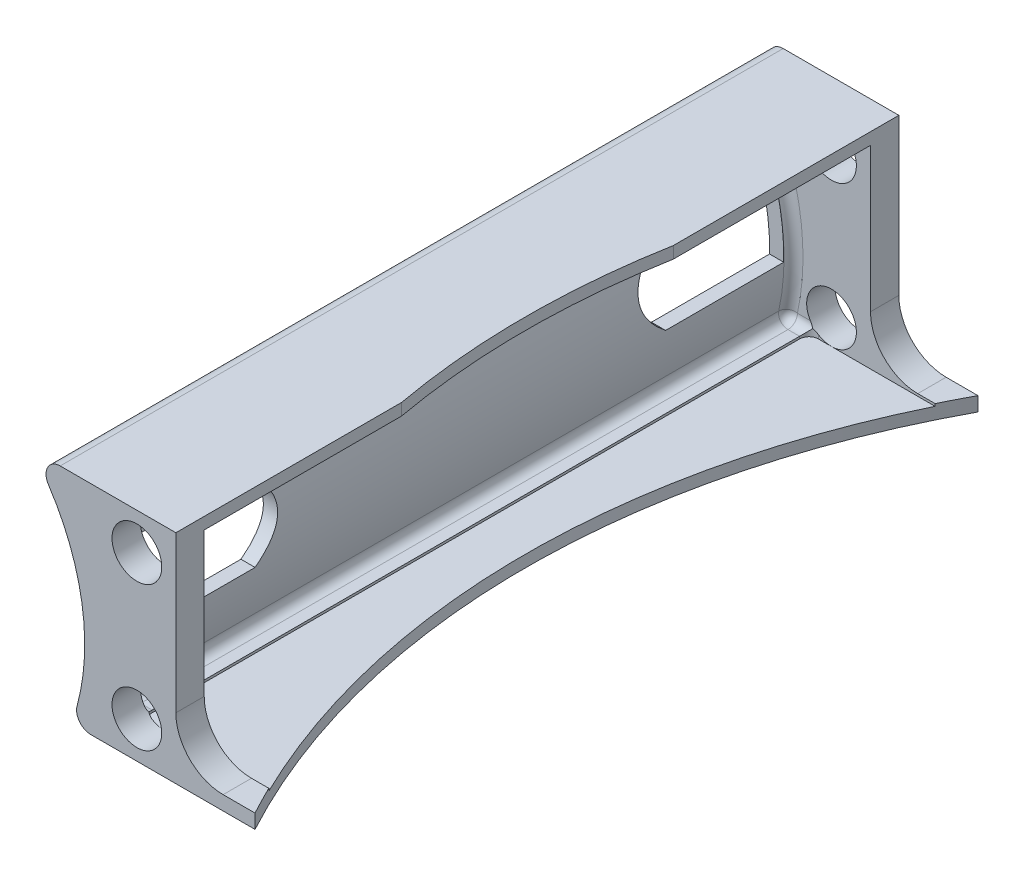
SolidWorks part; units mm, degrees
ref_plane "Alzado" through (0, 0, 0) normal (0, 0, 1) x (1, 0, 0)
ref_plane "Planta" through (0, 0, 0) normal (0, 1, 0) x (1, 0, 0)
ref_plane "Vista lateral" through (0, 0, 0) normal (1, 0, 0) x (0, 0, -1)
sketch "Croquis1" plane through (0, 0, 0) normal (0, 0, 1) x (1, 0, 0)
  line L0 (0, 0) -> (250, 0) construction
  line L1 (47.2783, -15.875) -> (82.0398, -15.875)
  line L2 (40.8073, 30.125) -> (82.0398, 30.125)
  line L3 (43.1739, -15.875) -> (0, -15.875) construction
  line L4 (53.5698, 30.125) -> (53.5698, 22.947) construction
  line L5 (0, 0) -> (0, 34.925) construction
  line L6 (82.0398, 30.125) -> (82.0398, -15.875)
  line L7 (34.7633, 30.125) -> (-5.6174, 14.8479) construction
  line L8 (-5.5, 6.4807) -> (-5.5, -6.4807) construction
  line L9 (5.5, 6.4807) -> (5.5, -6.4807) construction
  arc A0 (-5.5, -6.4807) -> (5.5, -6.4807) centre (0, 0) ccw construction
  circle A2 centre (0, 0) radius 15.875 construction
  arc A5 (44.3837, -12.0867) -> (38.3089, 25.4643) centre (0, 0) ccw
  arc A6 (5.5, 6.4807) -> (-5.5, 6.4807) centre (0, 0) ccw construction
  arc A7 (47.2783, -15.875) -> (44.3837, -12.0867) centre (47.2783, -12.875) cw
  arc A8 (38.3089, 25.4643) -> (40.8073, 30.125) centre (40.8073, 27.125) cw
  dimension "D1" = 17
  dimension "D3" = 3
  dimension "D4" = 31.75
  dimension "D5" = 92
  dimension "D2" = 250
  dimension "D6" = 46
  dimension "D7" = 12.7625
  dimension "D8" = 28.47
  dimension "D9" = 5.5
extrude "Saliente-Extruir1" add sketch "Croquis1" along normal blind 6
sketch "Croquis6" plane through (0, 0, 0) normal (0, 0, -1) x (-1, 0, 0)
  line L0 (-61.4235, 30.125) -> (-61.4235, -15.875) construction
  line L1 (-82.0398, 30.125) -> (-40.8073, 30.125) construction
  line L2 (-47.2783, -15.875) -> (-82.0398, -15.875) construction
  line L3 (-45.8073, 27.125) -> (-40.8073, 27.125)
  line L4 (-47.2783, -12.875) -> (-52.2783, -12.875)
  line L5 (-45.8073, 27.125) -> (-45.8073, 30.125)
  line L6 (-45.8073, 30.125) -> (-40.8073, 30.125)
  line L7 (-52.2783, -12.875) -> (-52.2783, -15.875)
  line L8 (-52.2783, -15.875) -> (-47.2783, -15.875)
  arc A9 (-38.3089, 25.4643) -> (-40.8073, 30.125) centre (-40.8073, 27.125) ccw
  arc A10 (-38.3089, 25.4643) -> (-44.3837, -12.0867) centre (0, 0) ccw
  arc A11 (-40.8073, 27.125) -> (-47.2783, -12.875) centre (0, 0) ccw
  arc A12 (-40.8073, 27.125) -> (-47.2783, -12.875) centre (0, 0) ccw
  arc A13 (-47.2783, -15.875) -> (-44.3837, -12.0867) centre (-47.2783, -12.875) ccw
  arc A14 (-38.3089, 25.4643) -> (-40.8073, 30.125) centre (-40.8073, 27.125) ccw
  arc A15 (-38.3089, 25.4643) -> (-44.3837, -12.0867) centre (0, 0) ccw
  arc A16 (-47.2783, -15.875) -> (-44.3837, -12.0867) centre (-47.2783, -12.875) ccw
  dimension "D1" = 3
  dimension "D2" = 5
  dimension "D3" = 5
  dimension "D4" = 0
extrude "Saliente-Extruir4" add sketch "Croquis6" along normal blind 141
sketch "Croquis7" plane through (0, 0, -141) normal (0, 0, -1) x (-1, 0, 0)
  line L0 (-82.0398, 30.125) -> (-40.8073, 30.125)
  line L1 (-82.0398, 30.125) -> (-82.0398, -15.875)
  line L2 (-82.0398, -15.875) -> (-47.2783, -15.875)
  arc A9 (-47.2783, -15.875) -> (-44.3837, -12.0867) centre (-47.2783, -12.875) ccw
  arc A10 (-38.3089, 25.4643) -> (-44.3837, -12.0867) centre (0, 0) ccw
  arc A11 (-38.3089, 25.4643) -> (-40.8073, 30.125) centre (-40.8073, 27.125) ccw
  arc A12 (-47.2783, -15.875) -> (-44.3837, -12.0867) centre (-47.2783, -12.875) ccw
  arc A13 (-38.3089, 25.4643) -> (-44.3837, -12.0867) centre (0, 0) ccw
  arc A14 (-38.3089, 25.4643) -> (-40.8073, 30.125) centre (-40.8073, 27.125) ccw
  dimension "D1" = 0
extrude "Saliente-Extruir5" add sketch "Croquis7" along normal blind 6
fillet "Redondeo10" radius 2 8 edges at (43.3073, 27.125, -141) (43.3073, 27.125, 0) (49.7783, -12.875, 0) (49.7783, -12.875, -141) (40.8073, 27.125, -70.5) (47.2783, -12.875, -70.5) (48.3711, 7.8252, -141) (48.3711, 7.8252, 0)
fillet "Redondeo11" radius 2 4 edges at (45.8073, 27.625, 0) (52.2783, -13.375, 0) (52.2783, -13.375, -141) (45.8073, 27.625, -141)
sketch "Croquis8" plane through (0, 0, -147) normal (0, 0, -1) x (-1, 0, 0)
  line L0 (-82.0398, 27.125) -> (-37.8073, 27.125) construction
  line L1 (-82.0398, 30.125) -> (-82.0398, -15.875) construction
  line L2 (-40.8073, 30.125) -> (-82.0398, 30.125) construction
  line L6 (-40.8073, 30.125) -> (-40.8073, 27.125) construction
  line L7 (-48.8073, 27.125) -> (-48.8073, 24.5529) construction
  line L8 (-47.2783, -15.875) -> (-52.2783, -15.875) construction
  line L9 (-82.0398, -15.875) -> (-47.2783, -15.875) construction
  line L10 (-82.0398, -12.875) -> (-57.0408, -12.875) construction
  line L11 (-52.2783, -15.875) -> (-52.2783, 0) construction
  line L12 (-45.8073, 30.125) -> (-45.8073, 27.125) construction
  line L24 (-82.0398, -3.5688) -> (-82.0398, -4.3625)
  line L26 (-57.0408, -8.1125) -> (-82.0398, -8.1125) construction
  line L35 (-82.0398, -12.875) -> (-82.0398, -11.8625)
  line L36 (-82.0398, 7.125) -> (-33.2045, 7.125) construction
  arc A0 (-38.3089, 25.4643) -> (-40.8073, 30.125) centre (-40.8073, 27.125) ccw construction
  circle A3 centre (-57.0408, -8.1125) radius 5.2625
  circle A4 centre (-47.2783, -12.875) radius 3 construction
  arc A5 (-47.2783, -15.875) -> (-44.3837, -12.0867) centre (-47.2783, -12.875) ccw construction
  circle A7 centre (-57.0408, 22.3625) radius 5.2625
  point P22 (-40.8073, 28.625)
  point P32 (-59.9766, -8.1125)
  dimension "D5" = 10.525
  dimension "D7" = 5
  dimension "D10" = 30.475
  dimension "D1" = 3
  dimension "D4" = 8
  dimension "D6" = 3
  dimension "D8" = 5
  dimension "D9" = 7.5
extrude "Cortar-Extruir5" cut sketch "Croquis8" against normal blind 161 contours A3 | A7 region at (57.0408, -8.1125, -147)
sketch "Croquis9" plane through (82.0398, 0, 0) normal (1, 0, 0) x (0, 0, -1)
  line L0 (141, 7.125) -> (0, 7.125) construction
  line L1 (141, 30.125) -> (141, -15.875) construction
  line L3 (70.5, 7.125) -> (70.5, -15.875) construction
  line L4 (139, -15.875) -> (2, -15.875) construction
  line L8 (138.937, 15.125) -> (138.937, -0.9147)
  line L11 (2.063, 15.125) -> (2.063, -0.9147)
  line L12 (138.937, -0.9147) -> (113.937, -0.9147)
  line L13 (2.063, 15.125) -> (27.063, 15.125)
  line L14 (2.063, -0.9147) -> (27.063, -0.9147)
  line L15 (138.937, 15.125) -> (113.937, 15.125)
  line L16 (139, 24.1397) -> (2, 24.1397) construction
  line L17 (2, -10.4485) -> (139, -10.4485) construction
  spline S0 degree 2 poles (113.937, 15.125) (103.4588, 7.3019) (113.937, -0.9147) knots 0 0 0 1 1 1
  spline S1 degree 2 poles (27.063, 15.125) (37.5412, 7.3019) (27.063, -0.9147) knots 0 0 0 1 1 1
  point P12 (32.3014, 7.111)
  dimension "D1" = 25
  dimension "D3" = 9.0147
  dimension "D2" = 25
  dimension "D4" = 9.5338
extrude "Cortar-Extruir4" cut sketch "Croquis9" against normal through all
sketch "Croquis10" plane through (0, 0, 0) normal (0, 0, -1) x (-1, 0, 0)
  line L0 (-82.0398, -15.875) -> (-82.0398, 30.125) construction
  line L1 (-44.6642, 30.125) -> (-82.0398, 30.125)
  line L2 (-44.6642, 30.125) -> (-44.6642, 27.625)
  line L3 (-44.6642, 27.625) -> (-82.0398, 27.625)
  line L4 (-82.0398, 30.125) -> (-82.0398, 27.625)
  point P4 (0, 0)
  dimension "D1" = 2.5
extrude "Saliente-Extruir6" add sketch "Croquis10" along normal blind 142
sketch "Croquis15" plane through (0, 0, 6) normal (0, 0, 1) x (1, 0, 0)
  line L1 (82.0398, -15.875) -> (50.9754, -15.875)
  line L2 (82.0398, -15.875) -> (82.0398, -13.375)
  line L3 (82.0398, -13.375) -> (50.9754, -13.375)
  line L4 (50.9754, -15.875) -> (50.9754, -13.375)
  dimension "D1" = 2.5
extrude "Saliente-Extruir8" add sketch "Croquis15" against normal blind 148
sketch "Croquis16" plane through (0, 0, 6) normal (0, 0, 1) x (1, 0, 0)
  line L0 (82.0398, 30.125) -> (69.0398, 30.125) construction
  line L1 (82.0398, 30.125) -> (40.8073, 30.125) construction
  line L2 (69.0398, 30.125) -> (69.0398, 16.125) construction
  line L3 (82.0398, 7.125) -> (45.4096, 7.3461) construction
  line L4 (82.0398, -15.875) -> (82.0398, 30.125) construction
  arc A0 (44.3837, -12.0867) -> (38.3089, 25.4643) centre (0, 0) ccw construction
  circle A1 centre (69.0398, 16.125) radius 1.5
  circle A2 centre (68.9321, -1.7174) radius 1.5
  dimension "D1" = 3
extrude "Cortar-Extruir6" cut sketch "Croquis16" against normal blind 156
sketch "Croquis18" plane through (0, 30.125, 0) normal (0, 1, 0) x (1, 0, 0)
  line L0 (82.0398, 147) -> (82.0398, -6)
  arc A0 (82.0398, 147) -> (82.0398, -6) centre (223.6795, 70.5) ccw
extrude "Cortar-Extruir7" cut sketch "Croquis18" against normal blind 64
sketch "Croquis19" plane through (0, 0, 6) normal (0, 0, 1) x (1, 0, 0)
  line L1 (82.0398, 30.125) -> (65.2908, 30.125)
  line L2 (82.0398, 30.125) -> (82.0398, -12.875)
  line L3 (82.0398, -12.875) -> (65.2908, -12.875)
  line L4 (65.2908, 30.125) -> (65.2908, -12.875)
  line L5 (47.2783, -15.875) -> (82.0398, -15.875) construction
  dimension "D2" = 3
extrude "Cortar-Extruir9" cut sketch "Croquis19" against normal blind 157
fillet "Redondeo12" radius 10 2 edges at (65.2908, -12.875, -144) (65.2908, -12.875, 3)
